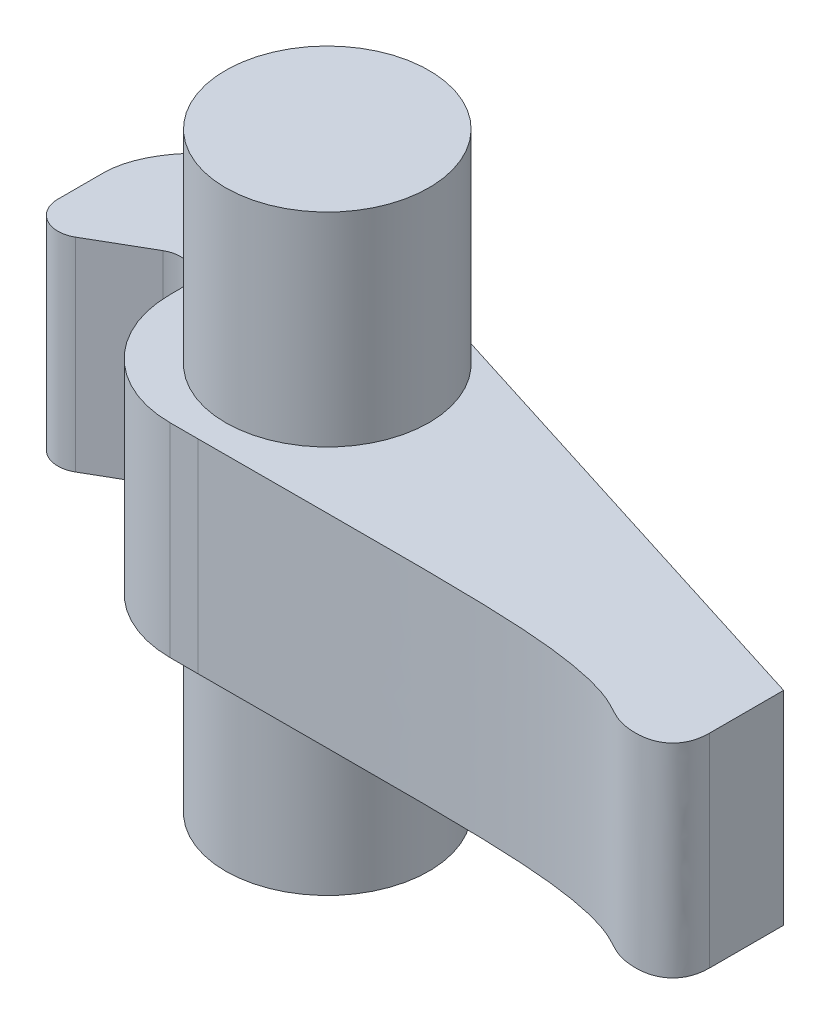
SolidWorks part; units mm, degrees
note: The reader was unsure of these and kept them because the rebuilt part matched: shared geometry of "Sketch1<3>".
ref_plane "Front Plane" through (0, 0, 0) normal (0, 0, 1) x (1, 0, 0)
ref_plane "Top Plane" through (0, 0, 0) normal (0, 1, 0) x (1, 0, 0)
ref_plane "Right Plane" through (0, 0, 0) normal (1, 0, 0) x (0, 0, -1)
sketch "Sketch1" plane through (0, 0, 0) normal (0, 1, 0) x (1, 0, 0)
  line L4 (0, -1.4) -> (0, 1.1) construction
  line L5 (5.5236, -0.5892) -> (5.5236, -1.3892)
  line L6 (0, -0.15) -> (0.3735, 1.0346) construction
  line L7 (0.3735, 1.0346) -> (5.5236, -0.5892)
  line L8 (5.5236, 55.0797) -> (5.5236, 56.7327) construction
  line L9 (-8.8236, -1.7892) -> (-8.1829, -1.7892) construction
  line L11 (1.4068, -1.4) -> (4.5596, -1.4) construction
  line L12 (0, -1.4) -> (-0.3, -1.4)
  line L13 (-3, 0.5872) -> (-3, 0.0864)
  line L14 (-2.55, -0.1734) -> (-1.95, 0.173)
  line L15 (-1.5, -0.0868) -> (-1.5, -0.2)
  line L16 (0.3735, 1.0346) -> (-1.5339, 1.6361)
  line L17 (-1.0196, 1.4739) -> (-2.0501, 1.7988) construction
  circle A3 centre (0, 0) radius 1.1
  arc A4 (-3, 0.0864) -> (-2.55, -0.1734) centre (-2.7, 0.0864) ccw
  arc A5 (-1.95, 0.173) -> (-1.5, -0.0868) centre (-1.8, -0.0868) cw
  arc A6 (-0.3, -1.4) -> (-1.5, -0.2) centre (-0.3, -0.2) cw
  spline S0 degree 3 poles (5.5236, -1.3892) (5.5236, -1.6556) (5.3109, -1.8018) (4.7916, -1.7734) (4.7727, -1.5967) (3.4151, -1.368) (2.1, -1.4) (0, -1.4) knots 0 0 0 0 0.200931 0.262112 0.572959 0.650634 1 1 1 1
  spline S1 degree 3 poles (-3, 0.5872) (-2.9931, 1.205) (-2.178, 1.8391) (-1.5339, 1.6361) knots 0 0 0 0 1 1 1 1
  point P4 (-3, -0.4332)
  point P19 (0, -0.15)
  point P30 (-1.5, -1.4)
  dimension "D9" = 0.3
  dimension "D14" = 1.5
  dimension "D12" = 1.4
  dimension "D11" = 2.2
  dimension "D24" = 7
  dimension "D16" = 1.2
  dimension "D3" = 60
  dimension "D4" = 17.5
  dimension "D5" = 1.5
  dimension "D6" = 2
  dimension "D7" = 5.4
  dimension "D8" = 0.4
  dimension "D10" = 0.8
  dimension "D13" = 0.4
  dimension "D15" = 1.4
  dimension "D17" = 0.1
extrude "Boss-Extrude1" add sketch "Sketch1" along normal blind 2.2
extrude "Boss-Extrude2" add sketch "Sketch1<3>" along normal blind 4.4 and the other way blind 2
sketch "Sketch1<3>" plane through (0, 0, 0) normal (0, 1, 0) x (1, 0, 0) same geometry as "Sketch1"
